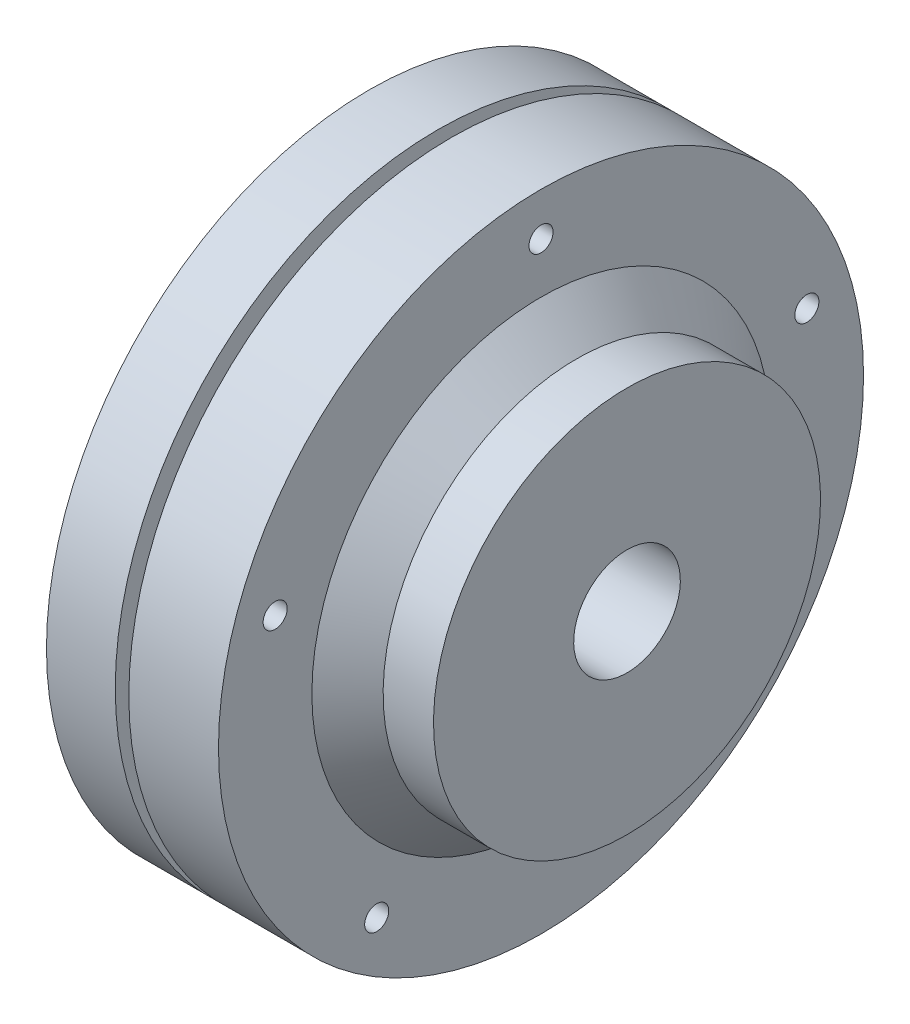
SolidWorks part; units mm, degrees
ref_plane "Front Plane" through (0, 0, 0) normal (0, 0, 1) x (1, 0, 0)
ref_plane "Top Plane" through (0, 0, 0) normal (0, 1, 0) x (1, 0, 0)
ref_plane "Right Plane" through (0, 0, 0) normal (1, 0, 0) x (0, 0, -1)
sketch "Sketch2" plane through (0, 0, 0) normal (-1, 0, 0) x (0, 0, 1)
  circle A0 centre (0, 0) radius 23.8125
  arc A1 (-2.4366, 23.6875) -> (-13.3595, 19.7119) centre (0, 0) ccw construction
  circle A2 centre (0, 20.6375) radius 1.4732 construction
  circle A3 centre (19.6274, 6.3773) radius 1.4732 construction
  circle A4 centre (12.1304, -16.6961) radius 1.4732 construction
  circle A5 centre (-12.1304, -16.6961) radius 1.4732 construction
  circle A6 centre (-19.6274, 6.3773) radius 1.4732 construction
  circle A7 centre (19.6274, 6.3773) radius 1.4732
  circle A8 centre (12.1304, -16.6961) radius 1.4732
  circle A9 centre (-12.1304, -16.6961) radius 1.4732
  circle A10 centre (-19.6274, 6.3773) radius 1.4732
  circle A11 centre (0, 20.6375) radius 1.4732
extrude "Boss-Extrude1" add sketch "Sketch2" along normal blind 5.08
hole_wizard "CSK for #4 Flat Head Machine Screw1" positions "Sketch3" profile "Sketch4" countersink size "#4" standard "ANSI Inch" end condition through all
sketch "Sketch3" plane through (-5.08, 0, 0) normal (-1, 0, 0) x (0, 0, 1)
  point P0 (0, 20.6375)
  point P3 (-19.6274, 6.3773)
  point P6 (-12.1304, -16.6961)
  point P9 (12.1304, -16.6961)
  point P12 (19.6274, 6.3773)
sketch "Sketch4" plane through (-5.08, 20.6375, 0) normal (0, 1, 0) x (0, 0, 1)
  line L0 (0, 0) -> (0, 5.08)
  line L1 (0, 5.08) -> (1.6319, 5.08)
  line L2 (1.6319, 5.08) -> (1.6319, 1.4098)
  line L3 (1.6319, 1.4098) -> (2.8575, 0)
  line L5 (2.8575, 0) -> (0, 0)
  line L6 (-1.632, 1.4098) -> (-2.8575, 0) construction
  line L11 (0, -6.35) -> (0, 107.95) construction
  dimension "Thru Hole Dia." = 3.2639
  dimension "Thru Hole Depth" = 5.08
  dimension "Near C'Sink Dia." = 5.715
  dimension "Near C'Sink Angle" = 82
sketch "Sketch1" plane through (0, 0, 0) normal (-1, 0, 0) x (0, 0, 1)
  arc A0 (-19.7748, 1.9978) -> (-14.8239, -13.2396) centre (0, 0) ccw
  arc A1 (-14.8239, -13.2396) -> (-14.1805, -13.3349) centre (-14.445, -12.9013) ccw
  arc A2 (-8.3003, -17.6072) -> (-14.1805, -13.3349) centre (-12.1304, -16.6961) ccw
  arc A3 (-8.3003, -17.6072) -> (-8.0108, -18.1896) centre (-7.8061, -17.7247) ccw
  arc A4 (-8.0108, -18.1896) -> (8.0108, -18.1896) centre (0, 0) ccw
  arc A5 (8.0108, -18.1896) -> (8.3003, -17.6072) centre (7.8061, -17.7247) ccw
  arc A6 (14.1805, -13.3349) -> (8.3003, -17.6072) centre (12.1304, -16.6961) ccw
  arc A7 (14.1805, -13.3349) -> (14.8239, -13.2396) centre (14.445, -12.9013) ccw
  arc A8 (14.8239, -13.2396) -> (19.7748, 1.9978) centre (0, 0) ccw
  arc A9 (19.7748, 1.9978) -> (19.3103, 2.4531) centre (19.2694, 1.9468) ccw
  arc A10 (17.0643, 9.3657) -> (19.3103, 2.4531) centre (19.6274, 6.3773) ccw
  arc A11 (17.0643, 9.3657) -> (17.1725, 10.0071) centre (16.7336, 9.7513) ccw
  arc A12 (17.1725, 10.0071) -> (4.2107, 19.4244) centre (0, 0) ccw
  arc A13 (4.2107, 19.4244) -> (3.6342, 19.1233) centre (4.1031, 18.9279) ccw
  arc A14 (-3.6342, 19.1233) -> (3.6342, 19.1233) centre (0, 20.6375) ccw
  arc A15 (-3.6342, 19.1233) -> (-4.2107, 19.4244) centre (-4.1031, 18.9279) ccw
  arc A16 (-4.2107, 19.4244) -> (-17.1725, 10.0071) centre (0, 0) ccw
  arc A17 (-17.1725, 10.0071) -> (-17.0643, 9.3657) centre (-16.7336, 9.7513) ccw
  arc A18 (-19.3103, 2.4531) -> (-17.0643, 9.3657) centre (-19.6274, 6.3773) ccw
  arc A19 (-19.3103, 2.4531) -> (-19.7748, 1.9978) centre (-19.2694, 1.9468) ccw
  arc A20 (-20.533, 2.0744) -> (-15.3922, -13.7472) centre (0, 0) ccw
  arc A21 (-19.3717, 3.2127) -> (-20.533, 2.0744) centre (-19.2694, 1.9468) ccw
  arc A22 (-19.3717, 3.2127) -> (-17.5604, 8.7873) centre (-19.6274, 6.3773) ccw
  arc A23 (-17.8309, 10.3907) -> (-17.5604, 8.7873) centre (-16.7336, 9.7513) ccw
  arc A24 (-4.3721, 20.1691) -> (-17.8309, 10.3907) centre (0, 0) ccw
  arc A25 (-2.9308, 19.4163) -> (-4.3721, 20.1691) centre (-4.1031, 18.9279) ccw
  arc A26 (-2.9308, 19.4163) -> (2.9308, 19.4163) centre (0, 20.6375) ccw
  arc A27 (4.3721, 20.1691) -> (2.9308, 19.4163) centre (4.1031, 18.9279) ccw
  arc A28 (17.8309, 10.3907) -> (4.3721, 20.1691) centre (0, 0) ccw
  arc A29 (17.5604, 8.7873) -> (17.8309, 10.3907) centre (16.7336, 9.7513) ccw
  arc A30 (17.5604, 8.7873) -> (19.3717, 3.2127) centre (19.6274, 6.3773) ccw
  arc A31 (20.533, 2.0744) -> (19.3717, 3.2127) centre (19.2694, 1.9468) ccw
  arc A32 (15.3922, -13.7472) -> (20.533, 2.0744) centre (0, 0) ccw
  arc A33 (13.7837, -13.9855) -> (15.3922, -13.7472) centre (14.445, -12.9013) ccw
  arc A34 (13.7837, -13.9855) -> (9.0416, -17.4308) centre (12.1304, -16.6961) ccw
  arc A35 (8.3179, -18.887) -> (9.0416, -17.4308) centre (7.8061, -17.7247) ccw
  arc A36 (-8.3179, -18.887) -> (8.3179, -18.887) centre (0, 0) ccw
  arc A37 (-9.0416, -17.4308) -> (-8.3179, -18.887) centre (-7.8061, -17.7247) ccw
  arc A38 (-9.0416, -17.4308) -> (-13.7837, -13.9855) centre (-12.1304, -16.6961) ccw
  arc A39 (-15.3922, -13.7472) -> (-13.7837, -13.9855) centre (-14.445, -12.9013) ccw
  arc A40 (-20.533, 2.0744) -> (-15.3922, -13.7472) centre (0, 0) ccw construction
  arc A41 (-19.3717, 3.2127) -> (-20.533, 2.0744) centre (-19.2694, 1.9468) ccw construction
  arc A42 (-19.3717, 3.2127) -> (-17.5604, 8.7873) centre (-19.6274, 6.3773) ccw construction
  arc A43 (-17.8309, 10.3907) -> (-17.5604, 8.7873) centre (-16.7336, 9.7513) ccw construction
  arc A44 (-4.3721, 20.1691) -> (-17.8309, 10.3907) centre (0, 0) ccw construction
  arc A45 (-2.9308, 19.4163) -> (-4.3721, 20.1691) centre (-4.1031, 18.9279) ccw construction
  arc A46 (-2.9308, 19.4163) -> (2.9308, 19.4163) centre (0, 20.6375) ccw construction
  arc A47 (4.3721, 20.1691) -> (2.9308, 19.4163) centre (4.1031, 18.9279) ccw construction
  arc A48 (17.8309, 10.3907) -> (4.3721, 20.1691) centre (0, 0) ccw construction
  arc A49 (17.5604, 8.7873) -> (17.8309, 10.3907) centre (16.7336, 9.7513) ccw construction
  arc A50 (17.5604, 8.7873) -> (19.3717, 3.2127) centre (19.6274, 6.3773) ccw construction
  arc A51 (20.533, 2.0744) -> (19.3717, 3.2127) centre (19.2694, 1.9468) ccw construction
  arc A52 (15.3922, -13.7472) -> (20.533, 2.0744) centre (0, 0) ccw construction
  arc A53 (13.7837, -13.9855) -> (15.3922, -13.7472) centre (14.445, -12.9013) ccw construction
  arc A54 (13.7837, -13.9855) -> (9.0416, -17.4308) centre (12.1304, -16.6961) ccw construction
  arc A55 (8.3179, -18.887) -> (9.0416, -17.4308) centre (7.8061, -17.7247) ccw construction
  arc A56 (-8.3179, -18.887) -> (8.3179, -18.887) centre (0, 0) ccw construction
  arc A57 (-9.0416, -17.4308) -> (-8.3179, -18.887) centre (-7.8061, -17.7247) ccw construction
  arc A58 (-9.0416, -17.4308) -> (-13.7837, -13.9855) centre (-12.1304, -16.6961) ccw construction
  arc A59 (-15.3922, -13.7472) -> (-13.7837, -13.9855) centre (-14.445, -12.9013) ccw construction
  dimension "D1" = 0
  dimension "D2" = 0.762
extrude "Boss-Extrude2" add sketch "Sketch1" along normal up to next (5.08 mm away) and the other way blind 3.175
sketch "Sketch5" plane through (3.175, 0, 0) normal (1, 0, 0) x (0, 0, -1)
  circle A0 centre (0, 0) radius 23.8125
  circle A1 centre (0, 0) radius 23.8125 construction
extrude "Boss-Extrude3" add sketch "Sketch5" along normal offset from surface (3.937 mm away) 12.7 from offset 0.508 separate body up to face at (-5.08, 20.6375, 2.8575)
sketch "Sketch6" plane through (3.683, 0, 0) normal (-1, 0, 0) x (0, 0, 1)
  circle A0 centre (0, 0) radius 23.8125 construction
  circle A1 centre (0, 0) radius 23.8125
  arc A20 (-4.3721, 20.1691) -> (-17.8309, 10.3907) centre (0, 0) ccw
  arc A21 (-17.8309, 10.3907) -> (-17.5604, 8.7873) centre (-16.7336, 9.7513) ccw
  arc A22 (-19.3717, 3.2127) -> (-17.5604, 8.7873) centre (-19.6274, 6.3773) ccw
  arc A23 (-19.3717, 3.2127) -> (-20.533, 2.0744) centre (-19.2694, 1.9468) ccw
  arc A24 (-20.533, 2.0744) -> (-15.3922, -13.7472) centre (0, 0) ccw
  arc A25 (-15.3922, -13.7472) -> (-13.7837, -13.9855) centre (-14.445, -12.9013) ccw
  arc A26 (-9.0416, -17.4308) -> (-13.7837, -13.9855) centre (-12.1304, -16.6961) ccw
  arc A27 (-9.0416, -17.4308) -> (-8.3179, -18.887) centre (-7.8061, -17.7247) ccw
  arc A28 (-8.3179, -18.887) -> (8.3179, -18.887) centre (0, 0) ccw
  arc A29 (8.3179, -18.887) -> (9.0416, -17.4308) centre (7.8061, -17.7247) ccw
  arc A30 (13.7837, -13.9855) -> (9.0416, -17.4308) centre (12.1304, -16.6961) ccw
  arc A31 (13.7837, -13.9855) -> (15.3922, -13.7472) centre (14.445, -12.9013) ccw
  arc A32 (15.3922, -13.7472) -> (20.533, 2.0744) centre (0, 0) ccw
  arc A33 (20.533, 2.0744) -> (19.3717, 3.2127) centre (19.2694, 1.9468) ccw
  arc A34 (17.5604, 8.7873) -> (19.3717, 3.2127) centre (19.6274, 6.3773) ccw
  arc A35 (17.5604, 8.7873) -> (17.8309, 10.3907) centre (16.7336, 9.7513) ccw
  arc A36 (17.8309, 10.3907) -> (4.3721, 20.1691) centre (0, 0) ccw
  arc A37 (4.3721, 20.1691) -> (2.9308, 19.4163) centre (4.1031, 18.9279) ccw
  arc A38 (-2.9308, 19.4163) -> (2.9308, 19.4163) centre (0, 20.6375) ccw
  arc A39 (-2.9308, 19.4163) -> (-4.3721, 20.1691) centre (-4.1031, 18.9279) ccw
  arc A40 (-4.3721, 20.1691) -> (-17.8309, 10.3907) centre (0, 0) ccw
  arc A41 (-17.8309, 10.3907) -> (-17.5604, 8.7873) centre (-16.7336, 9.7513) ccw
  arc A42 (-19.3717, 3.2127) -> (-17.5604, 8.7873) centre (-19.6274, 6.3773) ccw
  arc A43 (-19.3717, 3.2127) -> (-20.533, 2.0744) centre (-19.2694, 1.9468) ccw
  arc A44 (-20.533, 2.0744) -> (-15.3922, -13.7472) centre (0, 0) ccw
  arc A45 (-15.3922, -13.7472) -> (-13.7837, -13.9855) centre (-14.445, -12.9013) ccw
  arc A46 (-9.0416, -17.4308) -> (-13.7837, -13.9855) centre (-12.1304, -16.6961) ccw
  arc A47 (-9.0416, -17.4308) -> (-8.3179, -18.887) centre (-7.8061, -17.7247) ccw
  arc A48 (-8.3179, -18.887) -> (8.3179, -18.887) centre (0, 0) ccw
  arc A49 (8.3179, -18.887) -> (9.0416, -17.4308) centre (7.8061, -17.7247) ccw
  arc A50 (13.7837, -13.9855) -> (9.0416, -17.4308) centre (12.1304, -16.6961) ccw
  arc A51 (13.7837, -13.9855) -> (15.3922, -13.7472) centre (14.445, -12.9013) ccw
  arc A52 (15.3922, -13.7472) -> (20.533, 2.0744) centre (0, 0) ccw
  arc A53 (20.533, 2.0744) -> (19.3717, 3.2127) centre (19.2694, 1.9468) ccw
  arc A54 (17.5604, 8.7873) -> (19.3717, 3.2127) centre (19.6274, 6.3773) ccw
  arc A55 (17.5604, 8.7873) -> (17.8309, 10.3907) centre (16.7336, 9.7513) ccw
  arc A56 (17.8309, 10.3907) -> (4.3721, 20.1691) centre (0, 0) ccw
  arc A57 (4.3721, 20.1691) -> (2.9308, 19.4163) centre (4.1031, 18.9279) ccw
  arc A58 (-2.9308, 19.4163) -> (2.9308, 19.4163) centre (0, 20.6375) ccw
  arc A59 (-2.9308, 19.4163) -> (-4.3721, 20.1691) centre (-4.1031, 18.9279) ccw
  dimension "D1" = 0
extrude "Boss-Extrude4" add sketch "Sketch6" along normal up to surface (2.683 mm away)
hole_wizard "#50 (0.07) Diameter Hole1" positions "Sketch11" profile "Sketch13" hole size "#50" standard "ANSI Inch" end condition through all
sketch "Sketch11" plane through (1, 0, 0) normal (-1, 0, 0) x (0, 0, 1)
  point P0 (0, 20.6375)
  point P3 (19.6274, 6.3773)
  point P6 (12.1304, -16.6961)
  point P9 (-12.1304, -16.6961)
  point P12 (-19.6274, 6.3773)
sketch "Sketch13" plane through (1, 20.6375, 0) normal (0, 1, 0) x (0, 0, 1)
  line L0 (0, 0) -> (0, 6.62)
  line L1 (0, 6.62) -> (0.889, 6.62)
  line L2 (0.889, 6.62) -> (0.889, 0)
  line L5 (0.889, 0) -> (0, 0)
  line L11 (0, -6.35) -> (0, 107.95) construction
  dimension "Thru Hole Dia." = 1.778
  dimension "Thru Hole Depth" = 6.62
sketch "Sketch14" plane through (0, 0, 0) normal (0, 0, 1) x (1, 0, 0)
  line L0 (7.62, 0) -> (7.62, 16.9178)
  line L1 (7.62, -23.8125) -> (7.62, 23.8125) construction
  line L3 (13.97, 14.2875) -> (13.97, 0)
  line L4 (13.97, 0) -> (7.62, 0)
  line L5 (13.97, 14.2875) -> (10.2503, 14.2875)
  line L6 (10.2503, 14.2875) -> (7.62, 16.9178)
  line L7 (13.97, 0) -> (22.0322, 0) construction
  dimension "D1" = 6.35
  dimension "D2" = 45
  dimension "D3" = 28.575
revolve "Revolve1" add sketch "Sketch14" angle 360 about L7
sketch "Sketch15" plane through (13.97, 0, 0) normal (1, 0, 0) x (0, 0, -1)
  circle A0 centre (0, 0) radius 3.937
  dimension "D1" = 7.874
extrude "Cut-Extrude1" cut sketch "Sketch15" against normal through all
